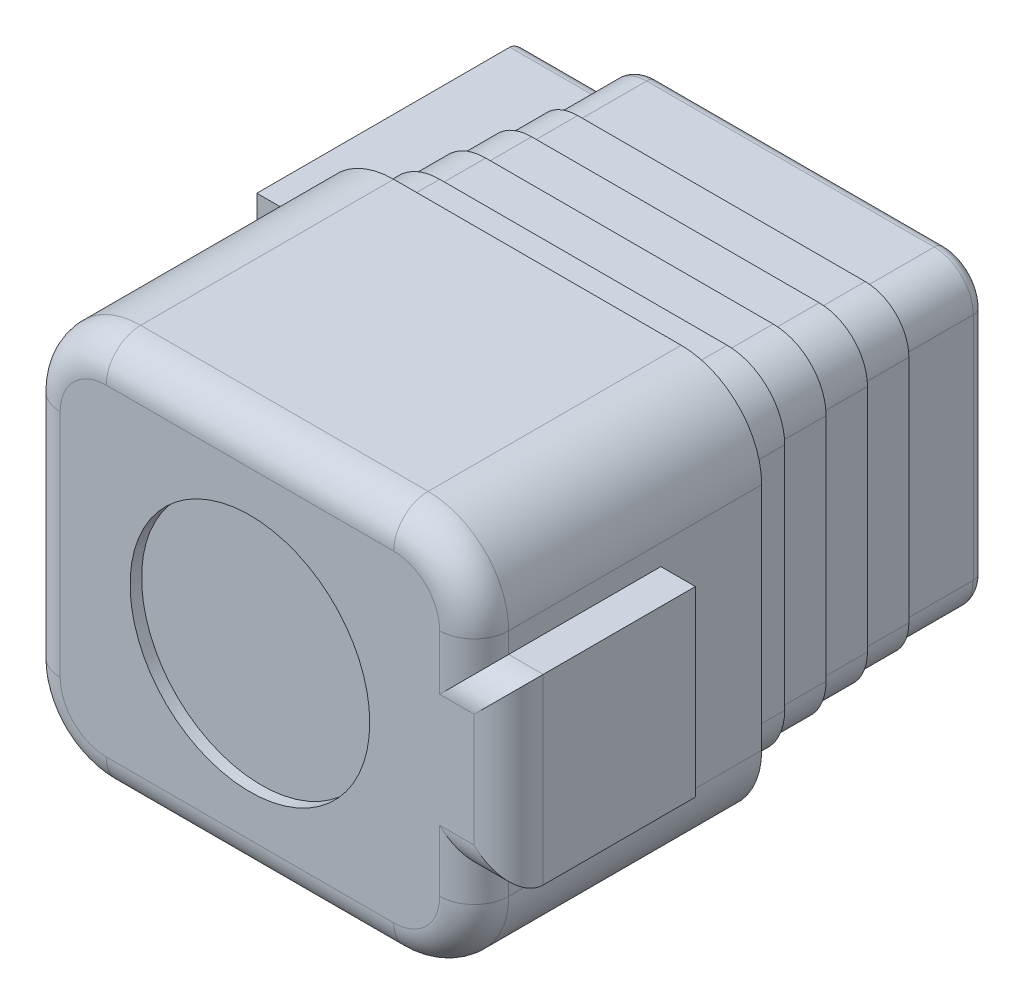
SolidWorks part; units mm, degrees
ref_plane "正面" through (0, 0, 0) normal (0, 0, 1) x (1, 0, 0)
ref_plane "平面" through (0, 0, 0) normal (0, 1, 0) x (1, 0, 0)
ref_plane "右側面" through (0, 0, 0) normal (1, 0, 0) x (0, 0, -1)
sketch "ｽｹｯﾁ1" plane through (0, 0, 0) normal (0, 0, 1) x (1, 0, 0)
  line L1 (7, 0) -> (32, 0)
  line L2 (0, 7) -> (0, 27)
  line L3 (7, 34) -> (32, 34)
  line L4 (39, 7) -> (39, 27)
  arc A0 (32, 34) -> (39, 27) centre (32, 27) cw
  arc A1 (32, 0) -> (39, 7) centre (32, 7) ccw
  arc A2 (7, 0) -> (0, 7) centre (7, 7) cw
  arc A3 (0, 27) -> (7, 34) centre (7, 27) cw
  point P7 (39, 34)
  point P12 (0, 0)
  point P15 (0, 34)
  dimension "D3" = 7
  dimension "D1" = 34
  dimension "D2" = 39
extrude "ﾎﾞｽ - 押し出し1" add sketch "ｽｹｯﾁ1" along normal blind 25
sketch "ｽｹｯﾁ2" plane through (0, 0, 0) normal (0, 0, -1) x (-1, 0, 0)
  line L8 (-37, 27) -> (-37, 7)
  line L9 (-32, 2) -> (-7, 2)
  line L10 (-2, 7) -> (-2, 27)
  line L11 (-7, 32) -> (-32, 32)
  line L12 (-37, 27) -> (-37, 7)
  line L13 (-32, 2) -> (-7, 2)
  line L14 (-2, 7) -> (-2, 27)
  line L15 (-7, 32) -> (-32, 32)
  arc A8 (-32, 32) -> (-37, 27) centre (-32, 27) ccw
  arc A9 (-37, 7) -> (-32, 2) centre (-32, 7) ccw
  arc A10 (-7, 2) -> (-2, 7) centre (-7, 7) ccw
  arc A11 (-2, 27) -> (-7, 32) centre (-7, 27) ccw
  arc A12 (-32, 32) -> (-37, 27) centre (-32, 27) ccw
  arc A13 (-37, 7) -> (-32, 2) centre (-32, 7) ccw
  arc A14 (-7, 2) -> (-2, 7) centre (-7, 7) ccw
  arc A15 (-2, 27) -> (-7, 32) centre (-7, 27) ccw
  dimension "D1" = 2
extrude "ﾎﾞｽ - 押し出し3" add sketch "ｽｹｯﾁ2" along normal blind 4
sketch "ｽｹｯﾁ3" plane through (0, 0, -4) normal (0, 0, -1) x (-1, 0, 0)
  line L8 (-39, 27) -> (-39, 7)
  line L9 (-32, 0) -> (-7, 0)
  line L10 (0, 7) -> (0, 27)
  line L11 (-7, 34) -> (-32, 34)
  line L12 (-39, 27) -> (-39, 7)
  line L13 (-32, 0) -> (-7, 0)
  line L14 (0, 7) -> (0, 27)
  line L15 (-7, 34) -> (-32, 34)
  line L36 (-32, 2.4) -> (-7, 2.4)
  line L37 (-2.4, 7) -> (-2.4, 27)
  line L38 (-7, 31.6) -> (-32, 31.6)
  line L39 (-36.6, 27) -> (-36.6, 7)
  line L40 (-32, 2.4) -> (-7, 2.4)
  line L41 (-2.4, 7) -> (-2.4, 27)
  line L42 (-7, 31.6) -> (-32, 31.6)
  line L43 (-36.6, 27) -> (-36.6, 7)
  arc A8 (-32, 34) -> (-39, 27) centre (-32, 27) ccw
  arc A9 (-39, 7) -> (-32, 0) centre (-32, 7) ccw
  arc A10 (-7, 0) -> (0, 7) centre (-7, 7) ccw
  arc A11 (0, 27) -> (-7, 34) centre (-7, 27) ccw
  arc A12 (-32, 34) -> (-39, 27) centre (-32, 27) ccw
  arc A13 (-39, 7) -> (-32, 0) centre (-32, 7) ccw
  arc A14 (-7, 0) -> (0, 7) centre (-7, 7) ccw
  arc A15 (0, 27) -> (-7, 34) centre (-7, 27) ccw
  arc A32 (-36.6, 7) -> (-32, 2.4) centre (-32, 7) ccw
  arc A33 (-7, 2.4) -> (-2.4, 7) centre (-7, 7) ccw
  arc A34 (-2.4, 27) -> (-7, 31.6) centre (-7, 27) ccw
  arc A35 (-32, 31.6) -> (-36.6, 27) centre (-32, 27) ccw
  arc A36 (-36.6, 7) -> (-32, 2.4) centre (-32, 7) ccw
  arc A37 (-7, 2.4) -> (-2.4, 7) centre (-7, 7) ccw
  arc A38 (-2.4, 27) -> (-7, 31.6) centre (-7, 27) ccw
  arc A39 (-32, 31.6) -> (-36.6, 27) centre (-32, 27) ccw
  dimension "D1" = 2
  dimension "D2" = 0.4
extrude "ﾎﾞｽ - 押し出し4" add sketch "ｽｹｯﾁ3" along normal blind 4 contours L43 A36 L40 A37 L41 A38 L42 A39
sketch "ｽｹｯﾁ4" plane through (0, 0, -8) normal (0, 0, -1) x (-1, 0, 0)
  line L8 (-36.2, 27) -> (-36.2, 7)
  line L9 (-32, 2.8) -> (-7, 2.8)
  line L10 (-2.8, 7) -> (-2.8, 27)
  line L11 (-7, 31.2) -> (-32, 31.2)
  line L12 (-36.2, 27) -> (-36.2, 7)
  line L13 (-32, 2.8) -> (-7, 2.8)
  line L14 (-2.8, 7) -> (-2.8, 27)
  line L15 (-7, 31.2) -> (-32, 31.2)
  arc A8 (-32, 31.2) -> (-36.2, 27) centre (-32, 27) ccw
  arc A9 (-36.2, 7) -> (-32, 2.8) centre (-32, 7) ccw
  arc A10 (-7, 2.8) -> (-2.8, 7) centre (-7, 7) ccw
  arc A11 (-2.8, 27) -> (-7, 31.2) centre (-7, 27) ccw
  arc A12 (-32, 31.2) -> (-36.2, 27) centre (-32, 27) ccw
  arc A13 (-36.2, 7) -> (-32, 2.8) centre (-32, 7) ccw
  arc A14 (-7, 2.8) -> (-2.8, 7) centre (-7, 7) ccw
  arc A15 (-2.8, 27) -> (-7, 31.2) centre (-7, 27) ccw
  dimension "D1" = 0.4
extrude "ﾎﾞｽ - 押し出し5" add sketch "ｽｹｯﾁ4" along normal blind 4
sketch "ｽｹｯﾁ5" plane through (0, 0, -12) normal (0, 0, -1) x (-1, 0, 0)
  line L8 (-35.8, 27) -> (-35.8, 7)
  line L9 (-32, 3.2) -> (-7, 3.2)
  line L10 (-3.2, 7) -> (-3.2, 27)
  line L11 (-7, 30.8) -> (-32, 30.8)
  line L12 (-35.8, 27) -> (-35.8, 7)
  line L13 (-32, 3.2) -> (-7, 3.2)
  line L14 (-3.2, 7) -> (-3.2, 27)
  line L15 (-7, 30.8) -> (-32, 30.8)
  arc A8 (-32, 30.8) -> (-35.8, 27) centre (-32, 27) ccw
  arc A9 (-35.8, 7) -> (-32, 3.2) centre (-32, 7) ccw
  arc A10 (-7, 3.2) -> (-3.2, 7) centre (-7, 7) ccw
  arc A11 (-3.2, 27) -> (-7, 30.8) centre (-7, 27) ccw
  arc A12 (-32, 30.8) -> (-35.8, 27) centre (-32, 27) ccw
  arc A13 (-35.8, 7) -> (-32, 3.2) centre (-32, 7) ccw
  arc A14 (-7, 3.2) -> (-3.2, 7) centre (-7, 7) ccw
  arc A15 (-3.2, 27) -> (-7, 30.8) centre (-7, 27) ccw
  dimension "D1" = 0.4
extrude "ﾎﾞｽ - 押し出し6" add sketch "ｽｹｯﾁ5" along normal blind 4
sketch "ｽｹｯﾁ6" plane through (0, 0, -16) normal (0, 0, -1) x (-1, 0, 0)
  line L8 (-35.4, 27) -> (-35.4, 7)
  line L9 (-32, 3.6) -> (-7, 3.6)
  line L10 (-3.6, 7) -> (-3.6, 27)
  line L11 (-7, 30.4) -> (-32, 30.4)
  line L12 (-35.4, 27) -> (-35.4, 7)
  line L13 (-32, 3.6) -> (-7, 3.6)
  line L14 (-3.6, 7) -> (-3.6, 27)
  line L15 (-7, 30.4) -> (-32, 30.4)
  arc A8 (-32, 30.4) -> (-35.4, 27) centre (-32, 27) ccw
  arc A9 (-35.4, 7) -> (-32, 3.6) centre (-32, 7) ccw
  arc A10 (-7, 3.6) -> (-3.6, 7) centre (-7, 7) ccw
  arc A11 (-3.6, 27) -> (-7, 30.4) centre (-7, 27) ccw
  arc A12 (-32, 30.4) -> (-35.4, 27) centre (-32, 27) ccw
  arc A13 (-35.4, 7) -> (-32, 3.6) centre (-32, 7) ccw
  arc A14 (-7, 3.6) -> (-3.6, 7) centre (-7, 7) ccw
  arc A15 (-3.6, 27) -> (-7, 30.4) centre (-7, 27) ccw
  dimension "D1" = 0.4
extrude "ﾎﾞｽ - 押し出し7" add sketch "ｽｹｯﾁ6" along normal blind 7
sketch "ｽｹｯﾁ7" plane through (3.6, 0, 0) normal (-1, 0, 0) x (0, 0, 1)
  line L1 (0, 27) -> (-23, 27)
  line L2 (0, 27) -> (0, 7)
  line L3 (0, 7) -> (-23, 7)
  line L4 (-23, 27) -> (-23, 7)
extrude "ﾎﾞｽ - 押し出し8" add sketch "ｽｹｯﾁ7" along normal blind 8.5
sketch "ｽｹｯﾁ8" plane through (39, 0, 0) normal (1, 0, 0) x (0, 0, -1)
  line L0 (-25, 17.2832) -> (0, 17.2832) construction
  line L1 (-25, 7) -> (-25, 27) construction
  line L2 (0, 7) -> (0, 27) construction
  line L4 (-8.7683, 25.2135) -> (-25, 25.2135)
  line L5 (-8.7683, 25.2135) -> (-8.7683, 9.353)
  line L6 (-8.7683, 9.353) -> (-25, 9.353)
  line L7 (-25, 25.2135) -> (-25, 9.353)
  line L8 (-8.7683, 25.2135) -> (-25, 9.353) construction
  line L9 (-8.7683, 9.353) -> (-25, 25.2135) construction
  point P6 (-16.8841, 17.2832)
extrude "ﾎﾞｽ - 押し出し9" add sketch "ｽｹｯﾁ8" along normal blind 3
fillet "ﾌｨﾚｯﾄ1" radius 3 12 edges at (39, 26.1067, 25) (40.5, 25.2135, 25) (42, 17.2832, 25) (40.5, 9.353, 25) (39, 8.1765, 25) (36.9497, 2.0503, 25) (19.5, 0, 25) (2.0503, 2.0503, 25) (0, 17, 25) (2.0503, 31.9497, 25) (19.5, 34, 25) (36.9497, 31.9497, 25)
fillet "ﾌｨﾚｯﾄ2" radius 1 10 edges at (19.5, 30.4, -23) (4.5958, 29.4042, -23) (-0.65, 27, -23) (-4.9, 17, -23) (-0.65, 7, -23) (4.5958, 4.5958, -23) (19.5, 3.6, -23) (34.4042, 4.5958, -23) (35.4, 17, -23) (34.4042, 29.4042, -23)
sketch "ｽｹｯﾁ9" plane through (0, 0, 25) normal (0, 0, 1) x (1, 0, 0)
  line L0 (3, 17) -> (39, 17) construction
  line L1 (3, 27) -> (3, 7) construction
  line L2 (39, 12.353) -> (39, 22.2135) construction
  line L3 (19.4955, 31.0673) -> (19.5, 3) construction
  line L5 (7, 3) -> (32, 3) construction
  circle A0 centre (19.4978, 17.0336) radius 10.4206
extrude "ｶｯﾄ - 押し出し1" cut sketch "ｽｹｯﾁ9" against normal blind 1
sketch "ｽｹｯﾁ10" plane through (0, 0, -23) normal (0, 0, -1) x (-1, 0, 0)
  line L0 (-34.4, 17) -> (3.9, 17) construction
  line L1 (-34.4, 27) -> (-34.4, 7) construction
  line L2 (3.9, 8) -> (3.9, 26) construction
  line L3 (-19.6339, 29.453) -> (-19.6339, 4.6) construction
  line L5 (-32, 4.6) -> (-7, 4.6) construction
  circle A0 centre (-19.6339, 17.0265) radius 10.1976
extrude "ｶｯﾄ - 押し出し2" cut sketch "ｽｹｯﾁ10" against normal blind 1
ref_axis "軸1" through (19.4978, 17.0336, 24) along (0, 0, 1)
ref_axis "軸2" through (19.6339, 17.0265, -22) along (0, 0, -1)
